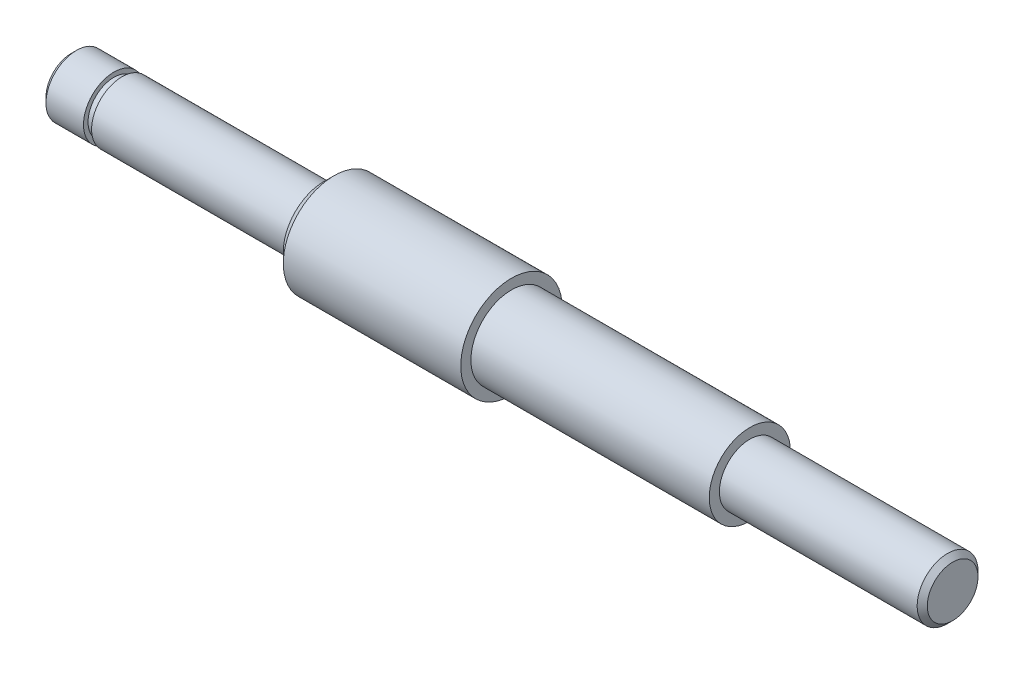
SolidWorks part; units mm, degrees
ref_plane "Alzado" through (0, 0, 0) normal (1, 0, 0) x (0, 1, 0)
ref_plane "Planta" through (0, 0, 0) normal (0, 0, 1) x (0, 1, 0)
ref_plane "Vista lateral" through (0, 0, 0) normal (0, 1, 0) x (-1, 0, 0)
sketch "Croquis1" plane through (0, 0, 0) normal (0, 1, 0) x (-1, 0, 0)
  line L0 (-43.45, 0) -> (-43.45, 3)
  line L1 (-43.45, 3) -> (-23.45, 3)
  line L2 (-23.45, 3) -> (-23.45, 4)
  line L3 (-23.45, 4) -> (0.05, 4)
  line L6 (43.45, 3) -> (43.45, 0)
  line L7 (-43.45, 0) -> (43.45, 0) construction
  line L9 (38.45, 3) -> (38.45, 2.55)
  line L10 (38.45, 2.55) -> (39.25, 2.55)
  line L11 (39.25, 2.55) -> (39.25, 3)
  line L12 (39.25, 3) -> (43.45, 3)
  line L14 (0.05, 4) -> (0.05, 5)
  line L15 (0.05, 5) -> (18.55, 5)
  line L16 (18.55, 5) -> (18.55, 3)
  line L17 (18.55, 3) -> (38.45, 3)
  line L18 (-43.45, 0) -> (43.45, 0)
  point P6 (43.45, 1.5)
  dimension "D2" = 6
  dimension "D4" = 8
  dimension "D8" = 0.8
  dimension "D6" = 0.45
  dimension "D1" = 20
  dimension "D9" = 19.9
  dimension "D12" = 10
  dimension "D10" = 43.5
  dimension "D5" = 5
  dimension "D3" = 18.5
revolve "Revolución1" add sketch "Croquis1" angle 360 about L7
chamfer "Chaflán1" distance 0.5 angle 45 2 edges at (-43.45, 0, -3) (43.45, 0, -3)
chamfer "Chaflán2" distance 1 angle 45 1 edges at (-18.55, 0, -5)
equation "\"ancho_circlip\"=0.8"
equation "\"D8@Croquis1\"=\"ancho_circlip\""
equation "\"ranura_circlip\"=0.45"
equation "\"D6@Croquis1\"=\"ranura_circlip\""
